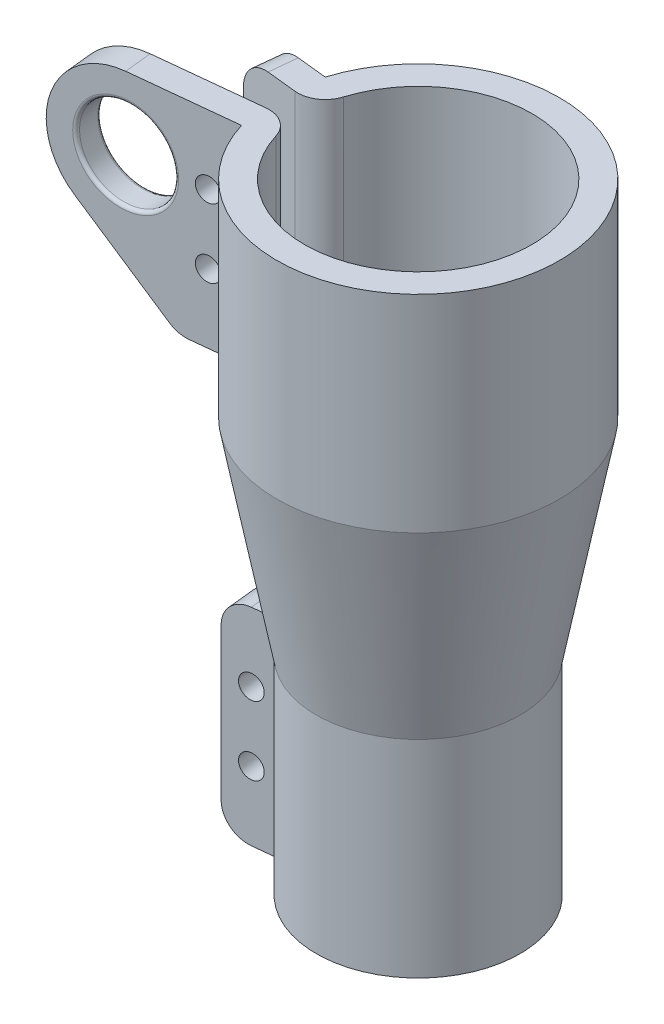
SolidWorks part; units mm, degrees
ref_plane "Front Plane" through (0, 0, 0) normal (0, 0, 1) x (1, 0, 0)
ref_plane "Top Plane" through (0, 0, 0) normal (0, 1, 0) x (1, 0, 0)
ref_plane "Right Plane" through (0, 0, 0) normal (1, 0, 0) x (0, 0, -1)
sketch "Sketch1" plane through (0, 0, 0) normal (0, 0, 1) x (1, 0, 0)
  line L0 (10.8, 0) -> (10.8, 30)
  line L1 (10.8, 30) -> (14.8, 30) construction
  line L2 (14.8, 30) -> (14.8, 0)
  line L3 (14.8, 0) -> (10.8, 0)
  line L4 (0, 0) -> (10.8, 0) construction
  line L5 (10.8, 30) -> (16.5, 60) construction
  line L6 (16.5, 60) -> (16.5, 90)
  line L7 (16.5, 90) -> (20.5, 90)
  line L8 (20.5, 90) -> (20.5, 60)
  line L9 (20.5, 60) -> (14.8, 30)
  line L10 (0, 0) -> (0, 41.987) construction
  line L11 (10.8, 30) -> (6.8, 30)
  line L12 (6.8, 30) -> (11.5, 55)
  line L13 (11.5, 55) -> (16.5, 60)
  dimension "D1" = 4
  dimension "D2" = 30
  dimension "D3" = 10.8
  dimension "D4" = 4
  dimension "D5" = 16.5
  dimension "D6" = 30
  dimension "D7" = 30
  dimension "D8" = 135
  dimension "D9" = 4
  dimension "D10" = 5
revolve "Revolve1" add sketch "Sketch1" angle 174 about L10
sketch "Sketch2" plane through (0, 0, 0) normal (-0.1045, 0, -0.9945) x (-0.9945, 0, 0.1045)
  line L0 (16.5, 90) -> (28.5, 90)
  line L1 (28.5, 90) -> (28.5, 60)
  line L2 (28.5, 60) -> (16.5, 60)
  line L3 (16.5, 60) -> (16.5, 90)
  line L5 (24.5, 90) -> (24.5, 80) construction
  line L6 (24.5, 80) -> (24.5, 70) construction
  line L7 (24.5, 70) -> (24.5, 60) construction
  line L9 (20.5, 75) -> (28.5, 75) construction
  line L10 (20.5, 60) -> (20.5, 90) construction
  line L11 (28.5, 90) -> (35.4041, 90)
  line L12 (28.5, 60) -> (42.1534, 71.4565)
  circle A0 centre (24.5, 80) radius 1.7
  circle A1 centre (24.5, 70) radius 1.7
  arc A2 (42.1534, 71.4565) -> (35.4041, 90) centre (35.4041, 79.5) ccw
  circle A3 centre (35.4041, 79.5) radius 6.5
  point P11 (16, 60)
  point P12 (16, 60)
  point P21 (24.5, 75)
  point P22 (36.3928, 80)
  point P26 (0, 0)
  line M9 (20.5, 60) -> (20.5, 90)
  line M10 (20.5, 90) -> (16.5, 90)
  line M11 (16.5, 90) -> (16.5, 60)
  dimension "D1" = 3.4
  dimension "D3" = 13
  dimension "D4" = 4
  dimension "D2" = 8
  dimension "D5" = 50
extrude "Boss-Extrude1" add sketch "Sketch2" against normal blind 4 contours L12 A2 L11 L1 A3 | L2 L1 L0 A1 A0 M9 | L2 M9 M10 M11
sketch "Sketch3" plane through (0, 0, 0) normal (-0.1045, 0, 0.9945) x (0.9945, 0, 0.1045)
  line L1 (-28.5, 90) -> (-28.5, 60)
  line L4 (-20.5, 60) -> (-20.5, 90) construction
  line L5 (-16.5, 60) -> (-11.5, 55) construction
  line L8 (-20.5, 75) -> (-28.5, 75) construction
  line L9 (-24.5, 70) -> (-24.5, 60) construction
  line L10 (-24.5, 80) -> (-24.5, 70) construction
  line L11 (-24.5, 90) -> (-24.5, 80) construction
  line L12 (-16.5, 60) -> (-16.5, 90)
  line L13 (-28.5, 60) -> (-16.5, 60)
  line L14 (-16.5, 90) -> (-28.5, 90)
  circle A2 centre (-24.5, 70) radius 1.5
  circle A3 centre (-24.5, 80) radius 1.5
  point P0 (-16, 60)
  point P31 (-24.5, 75)
  dimension "D1" = 8
  dimension "D2" = 3
extrude "Boss-Extrude2" add sketch "Sketch3" against normal blind 4
sketch "Sketch4" plane through (0, 0, 0) normal (-0.1045, 0, -0.9945) x (-0.9945, 0, 0.1045)
  line L0 (10.8, 30) -> (22.8, 30)
  line L1 (22.8, 30) -> (22.8, 0)
  line L2 (22.8, 0) -> (10.8, 0)
  line L3 (10.8, 0) -> (10.8, 30)
  line L4 (18.8, 30) -> (18.8, 20) construction
  line L5 (18.8, 20) -> (18.8, 10) construction
  line L6 (18.8, 10) -> (18.8, 0) construction
  line L7 (14.8, 15) -> (22.8, 15) construction
  line L9 (10.8, 0) -> (14.8, 0) construction
  line L10 (14.8, 0) -> (14.8, 30) construction
  line L11 (10.8, 30) -> (10.8, 0) construction
  circle A0 centre (18.8, 20) radius 1.7
  circle A1 centre (18.8, 10) radius 1.7
  point P12 (18.8, 15)
  point P13 (24.0724, 0.9607)
  point P14 (0, 0)
  point P15 (0, 0)
  point P16 (0, 0)
  point P18 (0, 0)
  point P19 (12.2, 0)
  point P22 (0, 0)
  point P23 (12.2, 10)
  point P24 (0, 0)
  point P25 (16.2, 10)
  point P28 (0, 0)
  point P29 (12.2, 30)
  dimension "D1" = 3.4
  dimension "D2" = 8
extrude "Boss-Extrude3" add sketch "Sketch4" against normal blind 4
sketch "Sketch5" plane through (0, 0, 0) normal (-0.1045, 0, 0.9945) x (0.9945, 0, 0.1045)
  line L1 (-22.8, 30) -> (-22.8, 0)
  line L4 (-14.8, 0) -> (-14.8, 30) construction
  line L5 (-10.8, 30) -> (-10.8, 0) construction
  line L8 (-14.8, 15) -> (-22.8, 15) construction
  line L9 (-18.8, 10) -> (-18.8, 0) construction
  line L10 (-18.8, 20) -> (-18.8, 10) construction
  line L11 (-18.8, 30) -> (-18.8, 20) construction
  line L12 (-10.8, 0) -> (-10.8, 30)
  line L13 (-22.8, 0) -> (-10.8, 0)
  line L14 (-10.8, 30) -> (-22.8, 30)
  circle A2 centre (-18.8, 10) radius 1.5
  circle A3 centre (-18.8, 20) radius 1.5
  point P0 (-12.2, 30)
  point P31 (-18.8, 15)
  dimension "D1" = 3
  dimension "D2" = 8
extrude "Boss-Extrude4" add sketch "Sketch5" against normal blind 4
ref_plane "Plane1" through (-8.7381, -1.6512, 0) normal (0.9826, 0.1857, 0) x (0, 0, -1)
sketch "Sketch6" plane through (-8.7381, -1.6512, 0) normal (0.9826, 0.1857, 0) x (0, 0, -1)
  line L0 (1.7031, 40.2113) -> (-1.7031, 40.2113) construction
  line L1 (1.547, 32.2113) -> (2.1428, 62.7421) construction
  line L2 (-1.547, 32.2113) -> (-2.1428, 62.7421) construction
  circle A0 centre (0, 40.2113) radius 2.9
  dimension "D2" = 5.8
  dimension "D1" = 8
extrude "Cut-Extrude2" cut sketch "Sketch6" along normal up to surface (17.039 mm away)
fillet "Fillet1" radius 4 11 edges at (-10.7408, 15, 1.1289) (-22.466, 30, -4.3723) (-22.466, 0, -4.3723) (-16.4096, 75, -1.7247) (-28.1348, 60, 4.9681) (-10.7408, 15, -1.1289) (-28.1348, 90, -4.9681) (-28.1348, 60, -4.9681) (-22.466, 30, 4.3723) (-22.466, 0, 4.3723) (-16.4096, 75, 1.7247)
fillet "Fillet2" radius 0.5 2 edges at (-41.2564, 79.5, 8.3583) (-41.6745, 79.5, 4.3802)
fillet "Fillet3" radius 2 4 edges at (-10.2227, 48.5051, -1.0744) (-7.3786, 33.2938, 0.7755) (-7.3786, 33.2938, -0.7755) (-10.2227, 48.5051, 1.0744)
